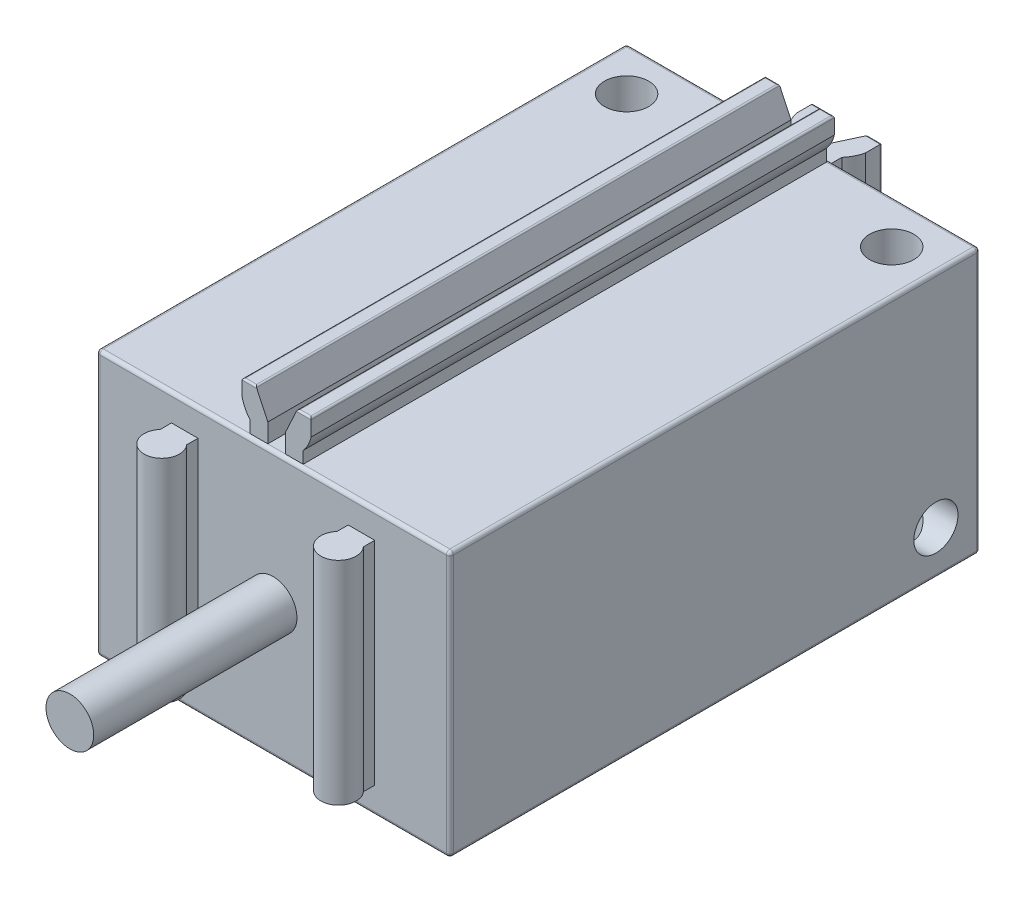
SolidWorks part; units mm, degrees
ref_plane "前视基准面" through (0, 0, 0) normal (0, 0, 1) x (1, 0, 0)
ref_plane "上视基准面" through (0, 0, 0) normal (0, 1, 0) x (1, 0, 0)
ref_plane "右视基准面" through (0, 0, 0) normal (1, 0, 0) x (0, 0, -1)
sketch "草图1" plane through (0, 0, 0) normal (0, 0, 1) x (1, 0, 0)
  line L1 (-10, -7.5) -> (10, -7.5)
  line L2 (-10, -7.5) -> (-10, 7.5)
  line L3 (-10, 7.5) -> (10, 7.5)
  line L4 (10, -7.5) -> (10, 7.5)
extrude "凸台-拉伸1" add sketch "草图1" against normal blind 30
sketch "草图2" plane through (0, 0, 0) normal (0, 1, 0) x (1, 0, 0)
  line L0 (-4.25, 0) -> (-5.75, 0)
  line L1 (-10, 0) -> (10, 0) construction
  line L2 (0, 1.4026) -> (0, -4.7973) construction
  line L3 (-5.75, 0) -> (-5.75, -0.6386)
  line L4 (-4.25, 0) -> (-4.25, -0.6386)
  line L5 (4.25, 0) -> (4.25, -0.6386)
  line L6 (5.75, 0) -> (5.75, -0.6386)
  line L7 (4.25, 0) -> (5.75, 0)
  arc A0 (-5.75, -0.6386) -> (-4.25, -0.6386) centre (-5, -1.3) ccw
  arc A1 (5.75, -0.6386) -> (4.25, -0.6386) centre (5, -1.3) cw
extrude "凸台-拉伸2" add sketch "草图2" along normal blind 6 and the other way blind 6
sketch "草图3" plane through (0, 0, 0) normal (0, 0, 1) x (1, 0, 0)
  circle A0 centre (0, 0) radius 1.35
extrude "凸台-拉伸3" add sketch "草图3" along normal blind 11.5
sketch "草图4" plane through (0, 0, 0) normal (0, 0, 1) x (1, 0, 0)
  line L0 (-1.5, 7.5) -> (-1.5, 8.1771)
  line L1 (10, 7.5) -> (-10, 7.5) construction
  line L2 (1.5, 7.5) -> (1.5, 8.1771)
  line L3 (-1.95, 10) -> (-1.1658, 10)
  line L4 (-1.95, 10) -> (-1.95, 9.0556)
  line L5 (1.95, 10) -> (1.95, 9.0556)
  line L6 (0, 7.1716) -> (0, 10.4474) construction
  line L7 (-1.5, 7.5) -> (-0.5, 7.5)
  line L8 (-0.5, 7.5) -> (-0.5, 8.5723)
  line L9 (0.5, 7.5) -> (0.5, 8.5723)
  line L10 (0.5, 8.5723) -> (1.1658, 10)
  line L11 (-0.5, 8.5723) -> (-1.1658, 10)
  line L12 (1.1658, 10) -> (1.95, 10)
  line L13 (0.5, 7.5) -> (1.5, 7.5)
  arc A1 (1.5, 8.1771) -> (1.95, 9.0556) centre (0, 9.5) ccw
  arc A2 (-1.95, 9.0556) -> (-1.5, 8.1771) centre (0, 9.5) ccw
extrude "凸台-拉伸4" add sketch "草图4" against normal blind 29.6 from offset 0.2 offset against normal yes
sketch "草图5" plane through (0, 7.5, 0) normal (0, 1, 0) x (-1, 0, 0)
  line L0 (1.5, -30) -> (1.5, -30.6771)
  line L1 (-10, -30) -> (10, -30) construction
  line L2 (-1.5, -30) -> (-1.5, -30.6771)
  line L3 (1.95, -32.5) -> (1.1658, -32.5)
  line L4 (1.95, -32.5) -> (1.95, -31.5556)
  line L5 (-1.95, -32.5) -> (-1.95, -31.5556)
  line L6 (1.5, -30) -> (0.5, -30)
  line L7 (0, -32.8437) -> (0, -29.6397) construction
  line L8 (0.5, -30) -> (0.5, -31.0723)
  line L9 (-0.5, -30) -> (-0.5, -31.0723)
  line L10 (0.5, -31.0723) -> (1.1658, -32.5)
  line L11 (-0.5, -31.0723) -> (-1.1658, -32.5)
  line L12 (-1.1658, -32.5) -> (-1.95, -32.5)
  line L13 (-0.5, -30) -> (-1.5, -30)
  arc A1 (-1.5, -30.6771) -> (-1.95, -31.5556) centre (0, -32) ccw
  arc A2 (1.95, -31.5556) -> (1.5, -30.6771) centre (0, -32) ccw
extrude "凸台-拉伸5" add sketch "草图5" against normal blind 14.6 from offset 0.2 offset against normal yes
fillet "圆角1" radius 0.1 16 edges at (1.1658, 10, -15) (1.5579, 10, -29.8) (1.95, 10, -15) (1.5579, 10, -0.2) (-1.95, 10, -15) (-1.5579, 10, -29.8) (-1.1658, 10, -15) (-1.5579, 10, -0.2) (1.1658, 0, -32.5) (1.5579, -7.3, -32.5) (1.95, 0, -32.5) (1.5579, 7.3, -32.5) (-1.95, 0, -32.5) (-1.5579, -7.3, -32.5) (-1.1658, 0, -32.5) (-1.5579, 7.3, -32.5)
fillet "圆角2" radius 0.2 12 edges at (-10, -7.5, -15) (-10, 0, -30) (-10, 7.5, -15) (-10, 0, 0) (10, 7.5, -15) (10, 0, -30) (10, -7.5, -15) (10, 0, 0) (0, -7.5, -30) (0, 7.5, -30) (0, -7.5, 0) (0, 7.5, 0)
sketch "草图6" plane through (0, 7.5, 0) normal (0, 1, 0) x (-1, 0, 0)
  circle A0 centre (7.5, -27.5) radius 1.25
  circle A1 centre (-7.5, -27.5) radius 1.25
extrude "切除-拉伸1" cut sketch "草图6" against normal through all
sketch "草图7" plane through (-10, 0, 0) normal (-1, 0, 0) x (0, 0, 1)
  circle A0 centre (-27.5, -5) radius 1.25
extrude "切除-拉伸2" cut sketch "草图7" against normal through all
sketch "草图8" plane through (0, 0, -30) normal (0, 0, -1) x (-1, 0, 0)
  circle A0 centre (-7.5, 0) radius 1.25
  circle A1 centre (7.5, 0) radius 1.25
extrude "切除-拉伸3" cut sketch "草图8" against normal blind 5
